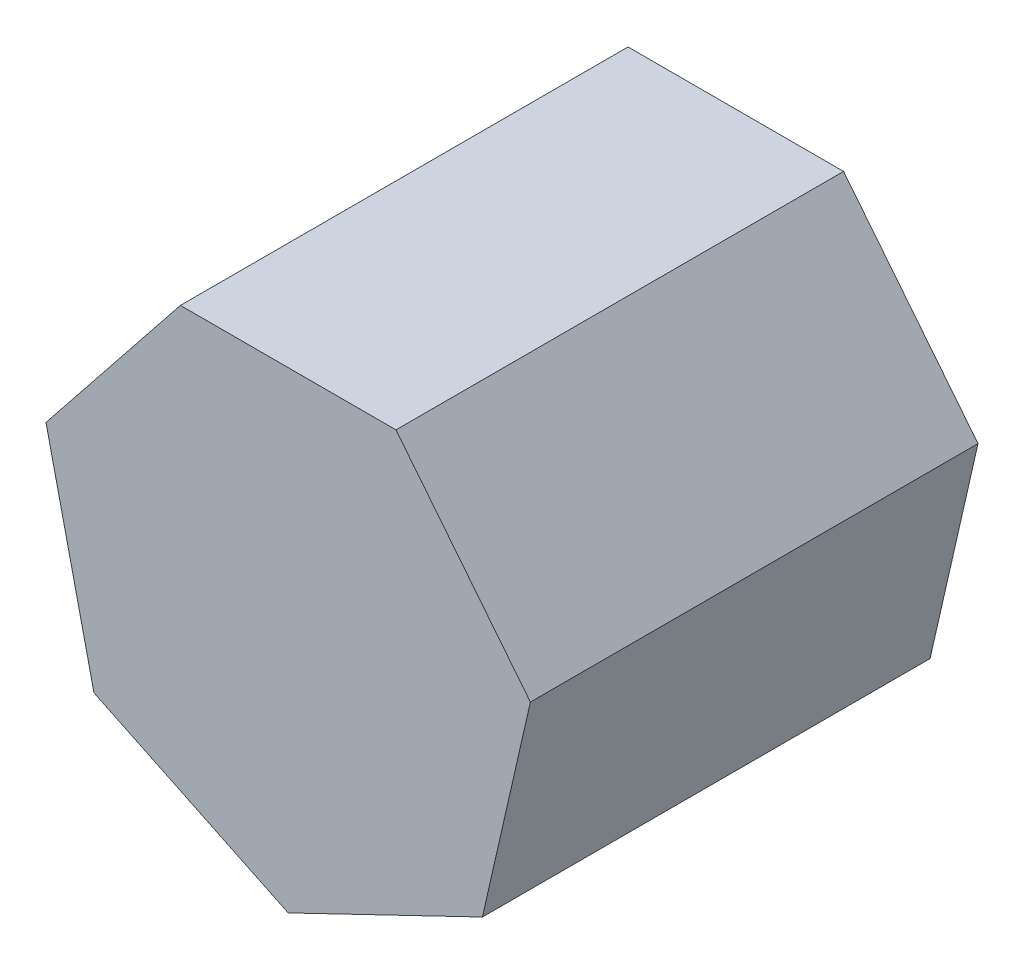
SolidWorks part; units mm, degrees
ref_plane "Front Plane" through (0, 0, 0) normal (0, 0, 1) x (1, 0, 0)
ref_plane "Top Plane" through (0, 0, 0) normal (0, 1, 0) x (1, 0, 0)
ref_plane "Right Plane" through (0, 0, 0) normal (1, 0, 0) x (0, 0, -1)
sketch "Sketch1" plane through (0, 0, 0) normal (0, 0, 1) x (1, 0, 0)
  line L1 (0, -110.9916) -> (86.7767, -69.2021)
  line L2 (86.7767, -69.2021) -> (108.2088, 24.698)
  line L3 (108.2088, 24.698) -> (48.1575, 100)
  line L4 (48.1575, 100) -> (-48.1575, 100)
  line L5 (-48.1575, 100) -> (-108.2088, 24.698)
  line L6 (-108.2088, 24.698) -> (-86.7767, -69.2021)
  line L7 (-86.7767, -69.2021) -> (0, -110.9916)
  circle A0 centre (0, 0) radius 100 construction
  point P1 (0, 0)
  dimension "D1" = 200
extrude "Boss-Extrude1" add sketch "Sketch1" along normal blind 200
sketch "Sketch2" plane through (-78.1831, 62.349, 0) normal (-0.7818, 0.6235, 0) x (0, 0, 1)
  text T0 "Andres" font "Century Gothic" height 20
extrude "Cut-Extrude1" cut sketch "Sketch2" against normal blind 1
